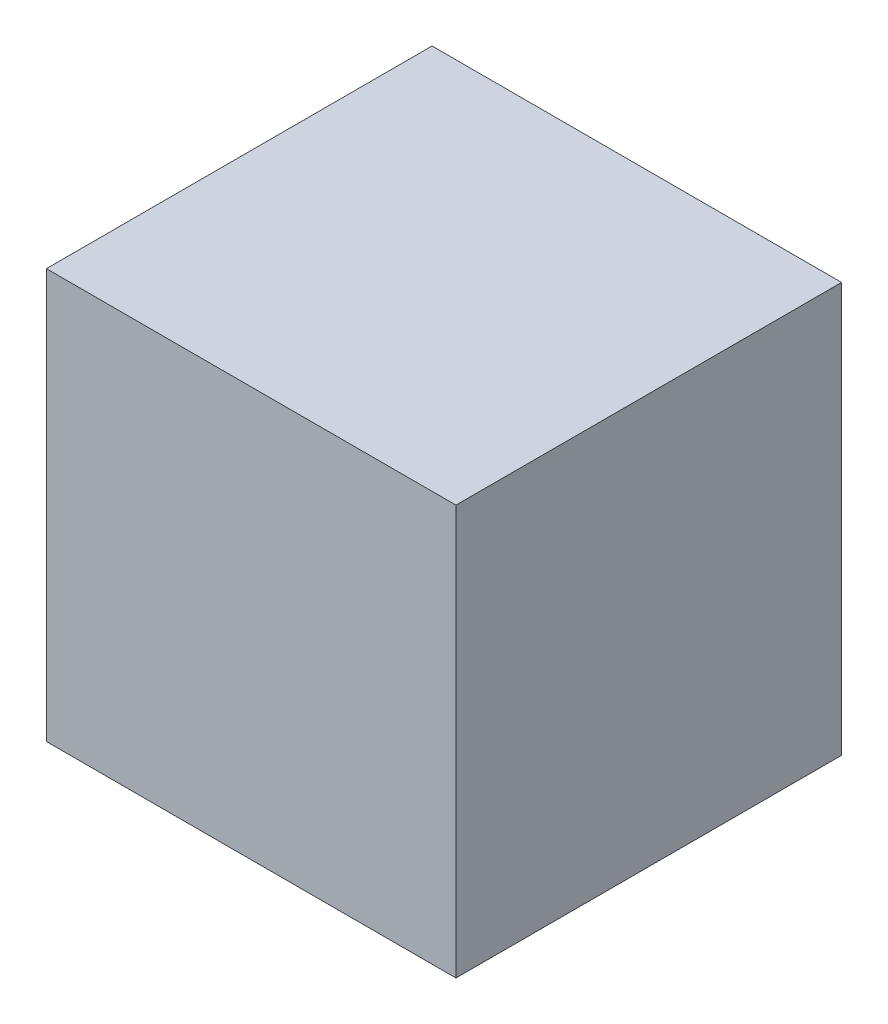
SolidWorks part; units mm, degrees
material "Plastiche personalizzate"
ref_plane "Piano frontale" through (0, 0, 0) normal (0, 0, 1) x (1, 0, 0)
ref_plane "Piano superiore" through (0, 0, 0) normal (0, 1, 0) x (1, 0, 0)
ref_plane "Piano destro" through (0, 0, 0) normal (1, 0, 0) x (0, 0, -1)
sketch "Schizzo1" plane through (0, 0, 0) normal (0, 0, 1) x (1, 0, 0)
  line L1 (50, -50) -> (-50, -50)
  line L2 (50, -50) -> (50, 50)
  line L3 (50, 50) -> (-50, 50)
  line L4 (-50, -50) -> (-50, 50)
  line L5 (50, -50) -> (-50, 50) construction
  line L6 (50, 50) -> (-50, -50) construction
  point P0 (0, 0)
  dimension "D1" = 100
extrude "Estrusione-Estrusione1" add sketch "Schizzo1" along normal blind 94.16
ref_plane "Piano1" through (0, 0, 0) normal (1, 0, 0) x (0, 0, -1)
ref_plane "Piano2" through (0, 0, 47.08) normal (0, 0, 1) x (1, 0, 0)
sketch "Sketch1" plane through (0, 50, 0) normal (0, 1, 0) x (1, 0, 0)
  line L0 (-50, 0) -> (0, -50)
  line L1 (0, -50) -> (50, 0)
  line L2 (0, -50) -> (0, -94.16)
  line L3 (50, -94.16) -> (-50, -94.16) construction
  circle A0 centre (0, -50) radius 70.7107
